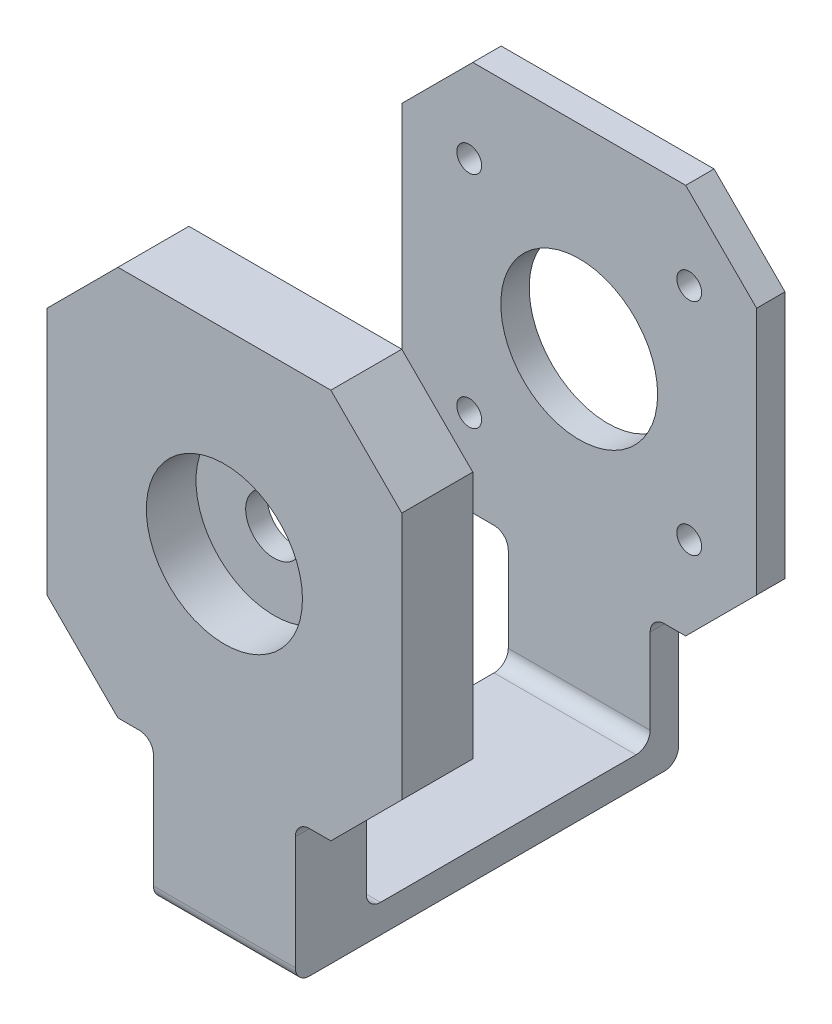
SolidWorks part; units mm, degrees
material "PLA"
ref_plane "Piano frontale" through (0, 0, 0) normal (0, 0, 1) x (1, 0, 0)
ref_plane "Piano superiore" through (0, 0, 0) normal (0, 1, 0) x (1, 0, 0)
ref_plane "Piano destro" through (0, 0, 0) normal (1, 0, 0) x (0, 0, -1)
sketch "Schizzo1" plane through (0, 0, 0) normal (0, 0, 1) x (1, 0, 0)
  line L5 (0, 0) -> (0, -67.5867) construction
  line L6 (-25, -27.5) -> (-10, -27.5)
  line L10 (-25, -27.5) -> (-25, 27.5)
  line L11 (-15.5, 15.5) -> (15.5, 15.5) construction
  line L12 (-15.5, 15.5) -> (-15.5, -15.5) construction
  line L13 (-15.5, -15.5) -> (15.5, -15.5) construction
  line L14 (15.5, 15.5) -> (15.5, -15.5) construction
  line L15 (-15.5, 15.5) -> (15.5, -15.5) construction
  line L16 (-15.5, -15.5) -> (15.5, 15.5) construction
  line L17 (-25, 27.5) -> (25, 27.5)
  line L18 (25, -27.5) -> (25, 27.5)
  line L22 (-25, -27.5) -> (25, 27.5) construction
  line L27 (-25, 27.5) -> (25, -27.5) construction
  line L29 (-10, -47.5) -> (10, -47.5)
  line L31 (-10, -47.5) -> (-10, -27.5)
  line L33 (10, -47.5) -> (10, -27.5)
  line L34 (-10, -47.5) -> (10, -27.5) construction
  line L35 (-10, -27.5) -> (10, -47.5) construction
  line L36 (10, -27.5) -> (25, -27.5)
  circle A0 centre (-15.5, 15.5) radius 1.75
  circle A1 centre (15.5, 15.5) radius 1.75
  circle A2 centre (15.5, -15.5) radius 1.75
  circle A3 centre (-15.5, -15.5) radius 1.75
  circle A4 centre (0, 0) radius 11.05
  point P4 (0, -37.5)
  point P14 (0, 0)
  dimension "D10" = 3.5
  dimension "D11" = 22.1
  dimension "D2" = 50
  dimension "D4" = 20
  dimension "D3" = 55
  dimension "D8" = 31
  dimension "D5" = 20
extrude "Estrusione-Estrusione1" add sketch "Schizzo1" along normal blind 4
sketch "Schizzo14" plane through (0, 0, 4) normal (0, 0, 1) x (1, 0, 0)
  line L0 (10, -47.5) -> (10, -27.5) construction
  line L1 (-10, -47.5) -> (10, -47.5)
  line L2 (-10, -47.5) -> (-10, -43.5)
  line L3 (-10, -43.5) -> (10, -43.5)
  line L4 (10, -47.5) -> (10, -43.5)
  dimension "D1" = 4
extrude "Estrusione-Estrusione2" add sketch "Schizzo14" along normal blind 40
sketch "Schizzo18" plane through (0, 0, 44) normal (0, 0, 1) x (1, 0, 0)
  line L0 (0, 0) -> (0, -60.5983) construction
  line L1 (-25, -27.5) -> (-10, -27.5)
  line L2 (-25, -27.5) -> (-25, 27.5)
  line L9 (-25, 27.5) -> (25, 27.5)
  line L10 (25, -27.5) -> (25, 27.5)
  line L11 (-25, -27.5) -> (25, 27.5) construction
  line L12 (-25, 27.5) -> (25, -27.5) construction
  line L13 (-10, -47.5) -> (10, -47.5)
  line L14 (-10, -47.5) -> (-10, -27.5)
  line L15 (10, -47.5) -> (10, -27.5)
  line L16 (-10, -47.5) -> (10, -27.5) construction
  line L17 (-10, -27.5) -> (10, -47.5) construction
  line L18 (10, -27.5) -> (25, -27.5)
  point P4 (0, -37.5)
  dimension "D4" = 50
  dimension "D5" = 55
  dimension "D6" = 20
  dimension "D7" = 20
extrude "Estrusione-Estrusione3" add sketch "Schizzo18" along normal blind 10
sketch "Schizzo19" plane through (0, 0, 54) normal (0, 0, 1) x (1, 0, 0)
  circle A0 centre (0, 0) radius 11
  dimension "D1" = 22
extrude "Taglio-Estrusione1" cut sketch "Schizzo19" against normal blind 7
sketch "Schizzo20" plane through (0, 0, 47) normal (0, 0, 1) x (1, 0, 0)
  circle A0 centre (0, 0) radius 4
  dimension "D1" = 8
extrude "Taglio-Estrusione2" cut sketch "Schizzo20" against normal blind 7
chamfer "Smusso1" distance 10 angle 45 8 edges at (25, 27.5, 2) (25, -27.5, 2) (-25, -27.5, 2) (-25, 27.5, 2) (25, -27.5, 49) (-25, -27.5, 49) (-25, 27.5, 49) (25, 27.5, 49)
fillet "Raccordo1" radius 2 8 edges at (0, -47.5, 0) (-10, -27.5, 2) (10, -27.5, 2) (0, -43.5, 4) (0, -43.5, 44) (0, -47.5, 54) (-10, -27.5, 49) (10, -27.5, 49)
